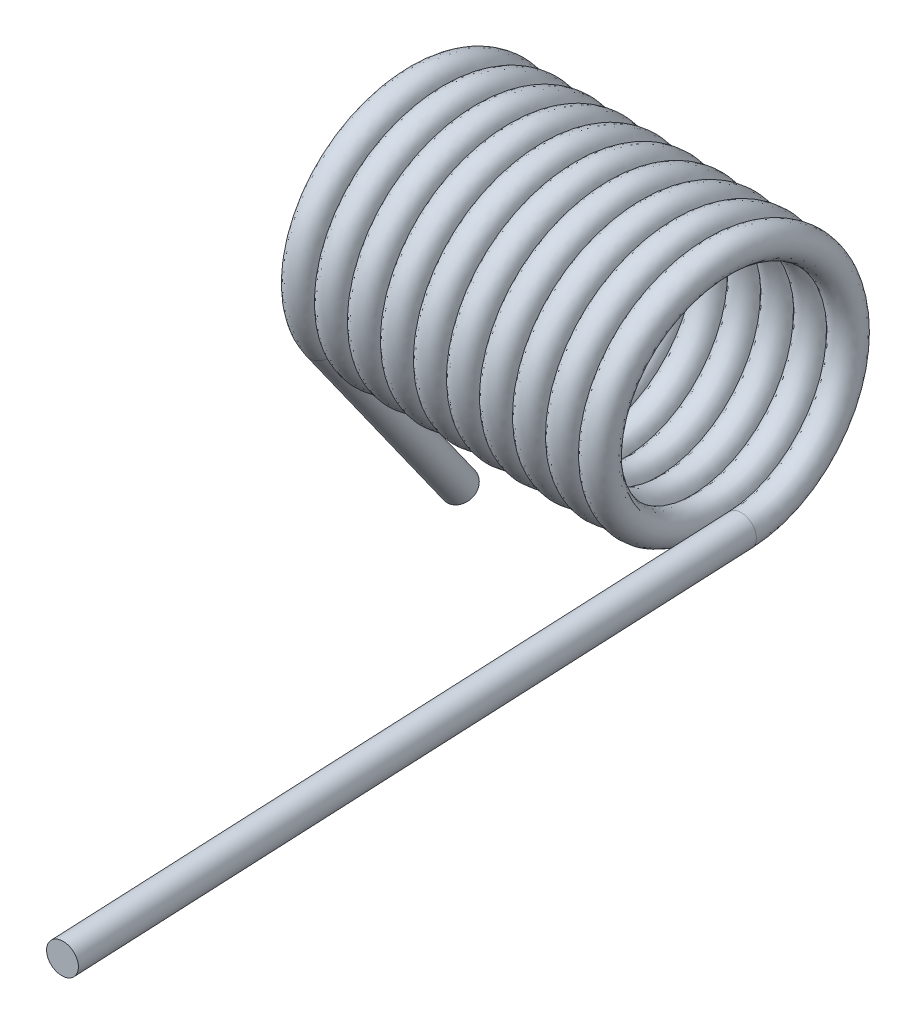
SolidWorks part; units mm, degrees
ref_plane "Front" through (0, 0, 0) normal (0, 0, 1) x (1, 0, 0)
ref_plane "Top" through (0, 0, 0) normal (0, 1, 0) x (1, 0, 0)
ref_plane "Right" through (0, 0, 0) normal (1, 0, 0) x (0, 0, -1)
sketch "Sketch1" plane through (0, 0, 0) normal (1, 0, 0) x (0, 0, -1)
  line L0 (0, -1.0033) -> (0, -1.3081) construction
  line L1 (-1.3081, 0) -> (-1.3081, -9.525) construction
  line L2 (0, -1.3081) -> (-9.525, -1.3081) construction
  line L3 (0, 0) -> (1.3081, 0) construction
  line L4 (0, 0) -> (-1.3081, 0) construction
  line L5 (-9.525, -1.3081) -> (-9.525, -1.0033) construction
  line L6 (-9.525, -1.0033) -> (0, -1.0033) construction
  line L7 (-1.3081, -9.525) -> (-1.0033, -9.525) construction
  line L8 (-1.0033, -9.525) -> (-1.0033, 0) construction
  circle A0 centre (0, 0) radius 1.3081 construction
  circle A1 centre (0, 0) radius 0.762 construction
  circle A2 centre (0, 0) radius 1.1557 construction
  point P7 (0, -1.1557)
  point P10 (0, 1.3081)
  dimension "OD" = 2.6162
  dimension "For Shaft Diameter" = 1.524
  dimension "Wire Diameter" = 0.3048
  dimension "Leg Length" = 9.525
  dimension "Deflection Angle" = 270
sketch "Sketch2" plane through (0, 0, 0) normal (1, 0, 0) x (0, 0, -1)
  circle A0 centre (0, 0) radius 1.1557 construction
  circle A2 centre (0, 0) radius 1.1557
curve "Helix/Spiral1" pitch 0.3302 height 3.2525 radius 1.1557 left hand yes centre (0, 0, 0) axis (-1, 0, 0) start towards (0, 0, -1)
ref_plane "Plane1" through (0, -1.1557, 0) normal (-0.0454, 0, -0.999) x (0.9987, -0.0232, -0.0454)
sketch "Sketch3" plane through (0, -1.1557, 0) normal (-0.0454, 0, -0.999) x (0.9987, -0.0232, -0.0454)
  circle A0 centre (0, 0) radius 0.1524
  dimension "D1" = 0.3048
sweep "Sweep1" add profiles "Sketch3" path "Helix/Spiral1"
sketch "Sketch4" plane through (0, 0, 0) normal (0.0454, 0, 0.999) x (-0.9987, 0.0232, 0.0454)
  circle A1 centre (-0.0269, 1.1554) radius 0.1524
  circle A2 centre (-0.0269, 1.1554) radius 0.1524
  dimension "D1" = 0
extrude "Extrude1" add sketch "Sketch4" along normal blind 7.112
sketch "Sketch5" plane through (-0.0067, -0.1194, -0.0868) normal (-0.0454, -0.8082, -0.5872) x (0.9528, 0.1416, -0.2687)
  circle A1 centre (-3.4462, 0.1255) radius 0.1524
  circle A2 centre (-3.4462, 0.1255) radius 0.1524
  dimension "D1" = 0
extrude "Extrude2" add sketch "Sketch5" along normal blind 2.54
sketch "Sketch6" plane through (0, 0, 0) normal (1, 0, 0) x (0, 0, -1)
  line L0 (0, 0) -> (-0.5207, 0.8576) construction
  circle A0 centre (0, 0) radius 1.0033
  circle A2 centre (0, 0) radius 1.0033 construction
sketch "Sketch7" plane through (0, 0, 0) normal (0, 1, 0) x (1, 0, 0)
  line L0 (0, 0) -> (-4.8058, 0) construction
equation "\"D4@Helix/Spiral1\" = \"Wire Diameter@Sketch1\" + .001"
equation "\"D1@Sketch3\"=\"Wire Diameter@Sketch1\""
